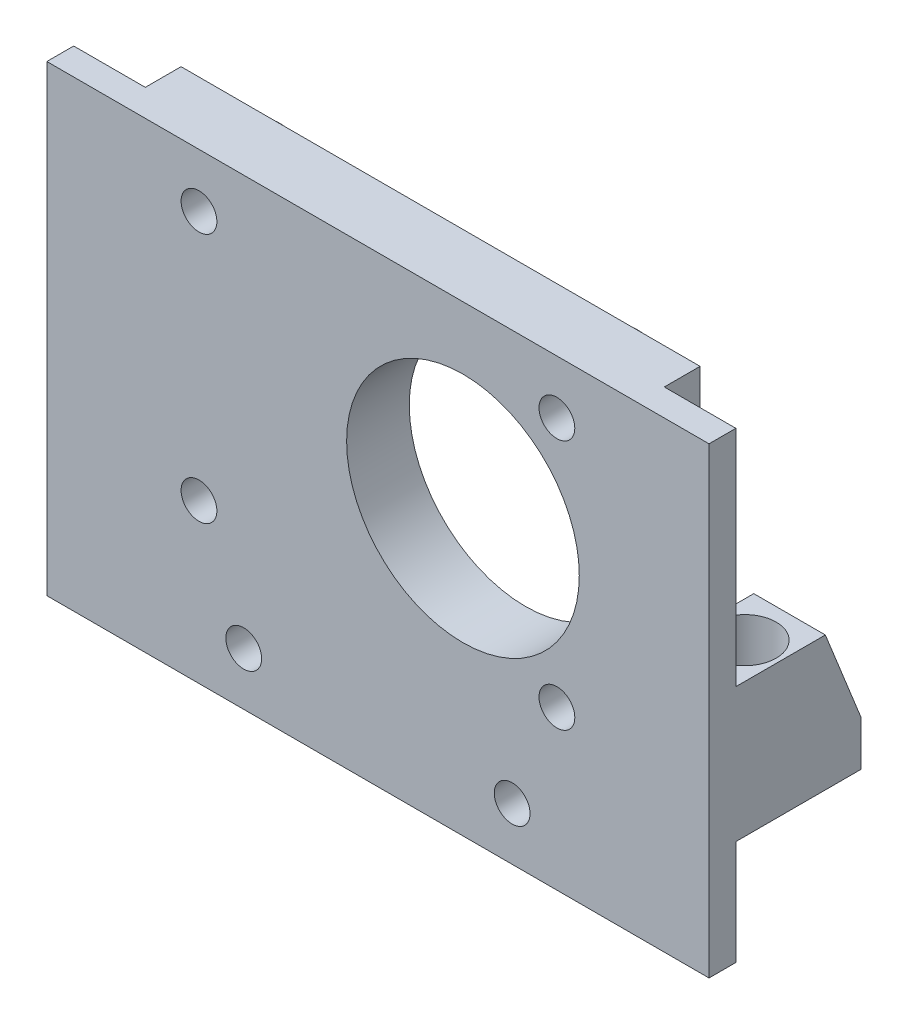
SolidWorks part; units mm, degrees
note: The reader was unsure of these and kept them because the rebuilt part matched: shared geometry of "Sketch1<4>", "Sketch2<2>", "Sketch3<3>", "Sketch1<6>", "Sketch2<3>", "Sketch2<4>", "Sketch1<7>".
material "ABS"
ref_plane "Front Plane" through (0, 0, 0) normal (0, 0, 1) x (1, 0, 0)
ref_plane "Top Plane" through (0, 0, 0) normal (0, 1, 0) x (1, 0, 0)
ref_plane "Right Plane" through (0, 0, 0) normal (1, 0, 0) x (0, 0, -1)
sketch "Sketch1" plane through (0, 0, 0) normal (0, 0, 1) x (1, 0, 0)
  line L1 (58, 41.836) -> (58, 1.836) construction
  line L2 (0, 41.836) -> (58, 41.836)
  line L3 (0, 41.836) -> (0, 1.836)
  line L4 (0, 1.836) -> (58, 1.836)
  line L5 (58, 41.836) -> (58, 1.836)
  line L6 (0, 41.836) -> (58, 1.836) construction
  line L7 (0, 1.836) -> (58, 41.836) construction
  line L8 (0, 18.8969) -> (0, 1.836) construction
  line L9 (58, 1.836) -> (0, 1.836) construction
  line L10 (58, 41.836) -> (0, 41.836) construction
  circle A1 centre (9, 35.836) radius 2
  circle A2 centre (9, 7.836) radius 2
  circle A3 centre (49, 35.836) radius 2
  circle A4 centre (38.5, 21.836) radius 13
  circle A5 centre (49, 7.836) radius 2
  circle A7 centre (49, 35.836) radius 4
  circle A8 centre (9, 35.836) radius 4
  circle A9 centre (9, 7.836) radius 4
  circle A10 centre (49, 7.836) radius 4
  point P19 (29, 21.836)
  dimension "D1" = 4
  dimension "D2" = 4
  dimension "D3" = 4
  dimension "D4" = 4
  dimension "D5" = 26
  dimension "D6" = 8
  dimension "D7" = 8
  dimension "D8" = 8
  dimension "D9" = 8
extrude "Boss-Extrude2" add sketch "Sketch1" along normal up to surface (6.0384 mm away) contours A7 A3 | A10 A5 | A9 A2 | A8 A1
sketch "Sketch3" plane through (0, 0, 6.0384) normal (0, 0, 1) x (1, 0, 0)
  line L0 (-45.6524, -9.864) -> (104.3476, -9.864) construction
  line L1 (-8, 1.836) -> (66, 1.836)
  line L2 (-8, 1.836) -> (-8, -9.864)
  line L3 (-8, -9.864) -> (66, -9.864)
  line L4 (66, 1.836) -> (66, -9.864)
  line L5 (-8, 1.836) -> (66, -9.864) construction
  line L6 (-8, -9.864) -> (66, 1.836) construction
  line L8 (-8, 1.836) -> (66, 1.836)
  line L9 (-8, 1.836) -> (-8, 6.836)
  line L10 (-8, 6.836) -> (66, 6.836)
  line L11 (66, 1.836) -> (66, 6.836)
  line L12 (-8, 1.836) -> (66, 6.836) construction
  line L13 (-8, 6.836) -> (66, 1.836) construction
  line L14 (0, 6.836) -> (58, 6.836)
  line L15 (0, 6.836) -> (0, 41.836)
  line L16 (0, 41.836) -> (58, 41.836)
  line L17 (58, 6.836) -> (58, 41.836)
  line L18 (0, 6.836) -> (58, 41.836) construction
  line L19 (0, 41.836) -> (58, 6.836) construction
  line L20 (58, 6.836) -> (66, 6.836)
  line L21 (58, 6.836) -> (58, 41.836)
  line L22 (58, 41.836) -> (66, 41.836)
  line L23 (66, 6.836) -> (66, 41.836)
  line L24 (58, 6.836) -> (66, 41.836) construction
  line L25 (58, 41.836) -> (66, 6.836) construction
  line L26 (0, 6.836) -> (-8, 6.836)
  line L27 (0, 6.836) -> (0, 41.836)
  line L28 (0, 41.836) -> (-8, 41.836)
  line L29 (-8, 6.836) -> (-8, 41.836)
  line L30 (0, 6.836) -> (-8, 41.836) construction
  line L31 (0, 41.836) -> (-8, 6.836) construction
  point P4 (29, -4.014)
  point P10 (29, 4.336)
  point P11 (62, 24.336)
  point P16 (29, 24.336)
  point P18 (-4, 24.336)
  circle M33 centre (49, 35.836) radius 4
  dimension "D1" = 74
  dimension "D2" = 35
  dimension "D3" = 58
  dimension "D4" = 5
  dimension "D5" = 11.7
  dimension "D6" = 8
extrude "Boss-Extrude4" add sketch "Sketch3" along normal blind 3
ref_plane "Plane1" through (0, 1.836, 0) normal (0, -1, 0) x (-1, 0, 0)
sketch "Sketch2" plane through (0, -9.864, 0) normal (0, 1, 0) x (1, 0, 0)
  line L0 (-45.6524, -6.0384) -> (104.3476, -6.0384) construction
  line L1 (0, 1.9616) -> (-8, 1.9616)
  line L2 (0, 1.9616) -> (0, -6.0384)
  line L3 (0, -6.0384) -> (-8, -6.0384)
  line L4 (-8, 1.9616) -> (-8, -6.0384)
  line L5 (0, 1.9616) -> (-8, -6.0384) construction
  line L6 (0, -6.0384) -> (-8, 1.9616) construction
  line L7 (66, -9.0384) -> (66, -6.0384) construction
  line L8 (58, -6.0384) -> (66, -6.0384)
  line L9 (58, -6.0384) -> (58, 7.9616)
  line L10 (58, 7.9616) -> (66, 7.9616)
  line L11 (66, -6.0384) -> (66, 7.9616)
  line L12 (58, -6.0384) -> (66, 7.9616) construction
  line L13 (58, 7.9616) -> (66, -6.0384) construction
  circle A0 centre (62, -1.0384) radius 2
  circle A1 centre (-4, -1.0384) radius 2
  point P4 (9.1026, -15.1411)
  point P12 (62, -1.0384)
  dimension "D3" = 4
  dimension "D5" = 4
  dimension "D6" = 8
  dimension "D1" = 8
  dimension "D2" = 14
  dimension "D4" = 8
  dimension "D7" = 5
  dimension "D8" = 4
  dimension "D9" = 5
  dimension "D10" = 4
  dimension "D11" = 8
extrude "Boss-Extrude3" add sketch "Sketch2" along normal blind 5 from offset 11.7
extrude "Cut-Extrude1" cut sketch "Sketch1<4>" along normal blind 10 contours A1 | A2 | A5 | A3 | A4
sketch "Sketch1<4>" plane through (0, 0, 0) normal (0, 0, 1) x (1, 0, 0) same geometry as "Sketch1"
sketch "Sketch4" plane through (66, 0, 0) normal (1, 0, 0) x (0, 0, -1)
  line L0 (7.9616, 6.836) -> (-6.0384, 41.836)
  line L1 (-6.0384, 41.836) -> (-6.0384, 6.836)
  line L2 (-6.0384, 6.836) -> (7.9616, 6.836)
extrude "Boss-Extrude5" add sketch "Sketch4" against normal up to surface (8 mm away) up to face at (58, 4.336, -0.9616)
sketch "Sketch6" plane through (-8, 0, 0) normal (-1, 0, 0) x (0, 0, 1)
  line L0 (-1.9616, 6.836) -> (6.0384, 14.9938)
  line L1 (6.0384, 6.836) -> (6.0384, 41.836) construction
  line L2 (-1.9616, 6.836) -> (6.0384, 6.836)
  line L3 (6.0384, 6.836) -> (6.0384, 14.9938)
extrude "Boss-Extrude7" add sketch "Sketch6" against normal up to surface (8 mm away) up to face at (0, 4.336, 2.0384)
extrude "Cut-Extrude2" cut sketch "Sketch2<2>" along normal through all contours A0 | A1
sketch "Sketch2<2>" plane through (0, -9.864, 0) normal (0, 1, 0) x (1, 0, 0) same geometry as "Sketch2"
sketch "Sketch5" plane through (0, 1.836, 0) normal (0, -1, 0) x (1, 0, 0)
  circle A0 centre (62, 1.0384) radius 3.5
  circle A1 centre (-4, 1.0384) radius 3
  dimension "D1" = 7
  dimension "D2" = 6
extrude "Cut-Extrude3" cut sketch "Sketch5" against normal through all from offset 6 offset against normal yes
extrude "Boss-Extrude8" add sketch "Sketch3<3>" against normal blind 4 contours L10 L17 L16 L15 M33 | L1 L11 L10 L9
sketch "Sketch3<3>" plane through (0, 0, 6.0384) normal (0, 0, 1) x (1, 0, 0) same geometry as "Sketch3"
extrude "Cut-Extrude5" cut sketch "Sketch1<6>" along normal through all both and the other way through all contours A4
sketch "Sketch1<6>" plane through (0, 0, 0) normal (0, 0, 1) x (1, 0, 0) same geometry as "Sketch1"
sketch "Sketch8" plane through (0, 41.836, 0) normal (0, 1, 0) x (1, 0, 0)
  line L0 (66, 7.9616) -> (58, 7.9616) construction
  line L1 (66, -6.0384) -> (58, -6.0384)
  line L2 (66, -6.0384) -> (66, 7.9616)
  line L3 (66, 7.9616) -> (58, 7.9616)
  line L4 (58, -6.0384) -> (58, 7.9616)
  line L5 (66, -6.0384) -> (58, 7.9616) construction
  line L6 (66, 7.9616) -> (58, -6.0384) construction
  line L8 (0, -6.0384) -> (-8, -6.0384)
  line L9 (0, -6.0384) -> (0, 5.2753)
  line L10 (0, 5.2753) -> (-8, 5.2753)
  line L11 (-8, -6.0384) -> (-8, 5.2753)
  line L12 (0, -6.0384) -> (-8, 5.2753) construction
  line L13 (0, 5.2753) -> (-8, -6.0384) construction
  point P4 (62, 0.9616)
  point P12 (-4, -0.3816)
extrude "Cut-Extrude6" cut sketch "Sketch8" against normal blind 25
sketch "Sketch9" plane through (-8, 0, 0) normal (-1, 0, 0) x (0, 0, 1)
  line L1 (6.0384, 1.836) -> (-3.9616, 1.836)
  line L2 (6.0384, 1.836) -> (6.0384, 6.836)
  line L3 (6.0384, 6.836) -> (-3.9616, 6.836)
  line L4 (-3.9616, 1.836) -> (-3.9616, 6.836)
  line L5 (6.0384, 1.836) -> (-3.9616, 6.836) construction
  line L6 (6.0384, 6.836) -> (-3.9616, 1.836) construction
  point P4 (1.0384, 4.336)
  dimension "D1" = 10
extrude "Boss-Extrude10" add sketch "Sketch9" against normal up to vertex
extrude "Cut-Extrude7" cut sketch "Sketch2<3>" along normal blind 25 contours A1
sketch "Sketch2<3>" plane through (0, -9.864, 0) normal (0, 1, 0) x (1, 0, 0) same geometry as "Sketch2"
sketch "Sketch10" plane through (0, 0, 9.0384) normal (0, 0, 1) x (1, 0, 0)
  line L0 (66, -9.864) -> (66, 41.836) construction
  line L1 (-8, -9.864) -> (66, -9.864)
  line L2 (-8, -9.864) -> (-8, 1.936)
  line L3 (-8, 1.936) -> (66, 1.936)
  line L4 (66, -9.864) -> (66, 1.936)
  line L5 (-8, -9.864) -> (66, 1.936) construction
  line L6 (-8, 1.936) -> (66, -9.864) construction
  line L7 (66, -3.964) -> (-8, -3.964) construction
  circle A0 centre (14, -3.964) radius 2
  circle A1 centre (44, -3.964) radius 2
  point P4 (29, -3.964)
  dimension "D4" = 4
  dimension "D5" = 4
  dimension "D1" = 11.8
  dimension "D2" = 15
  dimension "D3" = 15
extrude "Cut-Extrude8" cut sketch "Sketch10" against normal blind 25 contours A1 | A0
extrude "Cut-Extrude9" cut sketch "Sketch2<4>" along normal blind 25 contours A0
sketch "Sketch2<4>" plane through (0, -9.864, 0) normal (0, 1, 0) x (1, 0, 0) same geometry as "Sketch2"
extrude "Cut-Extrude10" cut sketch "Sketch1<7>" along normal blind 25 contours A2 | A1 | A3 | A5
sketch "Sketch1<7>" plane through (0, 0, 0) normal (0, 0, 1) x (1, 0, 0) same geometry as "Sketch1"
